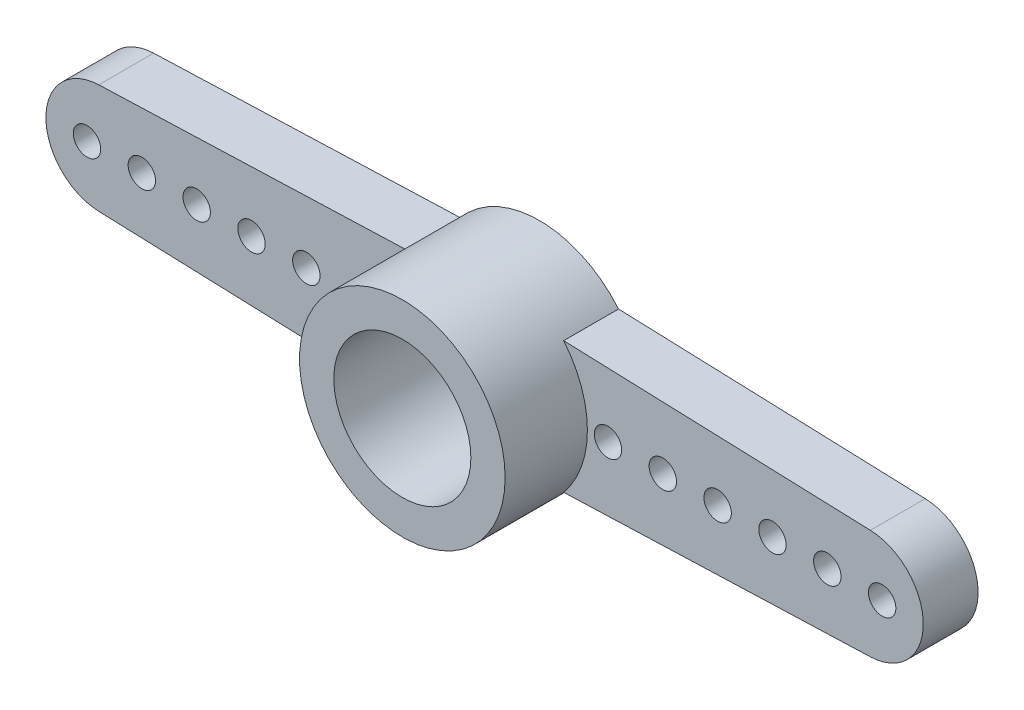
SolidWorks part; units mm, degrees
ref_plane "Спереди" through (0, 0, 0) normal (0, 0, 1) x (1, 0, 0)
ref_plane "Meio" through (0, 0, 0) normal (0, 1, 0) x (1, 0, 0)
ref_plane "Справа" through (0, 0, 0) normal (1, 0, 0) x (0, 0, -1)
sketch "Эскиз1" plane through (0, 0, 0) normal (0, 0, 1) x (1, 0, 0)
  line L0 (0, 0) -> (-14, 0)
  line L1 (-14.0708, 1.9987) -> (0, 2.4974)
  line L2 (-14.0708, -1.9987) -> (0, -2.4974)
  line L4 (14.0708, -1.9987) -> (0, -2.4974)
  line L5 (14.0708, 1.9987) -> (0, 2.4974)
  circle A0 centre (0, 0) radius 3.75
  circle A1 centre (0, 0) radius 2.5
  arc A2 (-13.967, -1.9997) -> (-14.0708, 1.9987) centre (-14, 0) cw
  arc A3 (13.967, -1.9997) -> (14.0708, 1.9987) centre (14, 0) ccw
  dimension "D1" = 7.5
  dimension "D2" = 5
  dimension "D4" = 2
  dimension "D3" = 14
extrude "Бобышка-Вытянуть3" add sketch "Эскиз1" along normal blind 2 contours L4 A3 L5 A0 | A2 L2 A0 L1 region at (-3.6586, -1.3206, 0) region at (9.339, 0, 0)
sketch "Эскиз2" plane through (0, 0, 2) normal (0, 0, 1) x (1, 0, 0)
  circle A0 centre (0, 0) radius 3.75
  circle A1 centre (0, 0) radius 2.5
  dimension "D1" = 5
extrude "Бобышка-Вытянуть5" add sketch "Эскиз2" along normal blind 3 separate body
sketch "Эскиз3" plane through (0, 0, 2) normal (0, 0, -1) x (-1, 0, 0)
  circle A0 centre (0, 0) radius 3.75
  circle A1 centre (0, 0) radius 2.5
extrude "Бобышка-Вытянуть6" add sketch "Эскиз3" along normal blind 2
sketch "Эскиз4" plane through (0, 0, 0) normal (0, 0, -1) x (-1, 0, 0)
  line L0 (-16, 0) -> (-14.5, 0)
  line L1 (-14.5, 0) -> (-12.5, 0)
  line L2 (-12.5, 0) -> (-10.5, 0)
  line L3 (-10.5, 0) -> (-8.5, 0)
  line L4 (-8.5, 0) -> (-6.5, 0)
  line L5 (-6.5, 0) -> (-4.5, 0)
  arc A0 (-14.0708, 1.9987) -> (-14.0708, -1.9987) centre (-14, 0) ccw construction
  circle A1 centre (-14.5, 0) radius 0.5
  circle A2 centre (-12.5, 0) radius 0.5
  circle A3 centre (-10.5, 0) radius 0.5
  circle A4 centre (-8.5, 0) radius 0.5
  circle A5 centre (-6.5, 0) radius 0.5
  circle A6 centre (-4.5, 0) radius 0.5
  circle A7 centre (4.5, 0) radius 0.5
  circle A8 centre (6.5, 0) radius 0.5
  circle A9 centre (8.5, 0) radius 0.5
  circle A10 centre (10.5, 0) radius 0.5
  circle A11 centre (12.5, 0) radius 0.5
  circle A12 centre (14.5, 0) radius 0.5
  dimension "D2" = 1
  dimension "D8" = 1
  dimension "D9" = 1
  dimension "D10" = 1
  dimension "D11" = 1
  dimension "D12" = 1
  dimension "D1" = 1.5
  dimension "D3" = 2
  dimension "D4" = 2
  dimension "D5" = 2
  dimension "D6" = 2
  dimension "D7" = 2
extrude "Вырез-Вытянуть1" cut sketch "Эскиз4" against normal blind 2 contours L1 A1 L0 | L0 A1 L1 | L3 A3 L2 | L2 A3 L3 | L4 A4 L3 | L3 A4 L4 | L5 A5 L4 | L4 A5 L5 | A6 | A7 | A8 | A9 | A10 | A11 | A12 | A2 | A12 region at (14.5, 0.2122, 0) region at (4.5, 0.4859, 0) region at (6.5, 0.2122, 0) region at (6.5, -0.2122, 0) region at (8.5, 0.2122, 0) region at (8.5, -0.2122, 0) region at (10.5, 0.2122, 0) region at (10.5, -0.2122, 0) region at (14.5, -0.2122, 0) region at (-4.5, 0, 0) region at (-6.5, 0, 0) region at (-8.5, 0, 0) region at (-10.5, 0, 0) region at (-12.5, 0, 0) region at (-14.5, 0, 0)
sketch "Эскиз5" plane through (0, 0, 0) normal (0, 0, -1) x (-1, 0, 0)
  circle A0 centre (0, 0) radius 2.5
extrude "Бобышка-Вытянуть7" add sketch "Эскиз5" against normal blind 1
sketch "Эскиз6" plane through (0, 0, 0) normal (0, 0, -1) x (-1, 0, 0)
  circle A0 centre (0, 0) radius 2.5
  dimension "D1" = 5
extrude "Вырез-Вытянуть2" cut sketch "Эскиз6" against normal blind 0.5
sketch "Эскиз7" plane through (0, 0, 0.5) normal (0, 0, -1) x (-1, 0, 0)
  circle A0 centre (0, 0) radius 1.25
  dimension "D1" = 2.5
extrude "Вырез-Вытянуть3" cut sketch "Эскиз7" against normal blind 5
sketch "Эскиз8" plane through (0, 0, 0.5) normal (0, 0, -1) x (-1, 0, 0)
  line L0 (-2.8252, -0.1999) -> (-2.8894, -0.2509)
move or copy body "Body-Move/Copy1" [suppressed] bodies to move or copy 113
